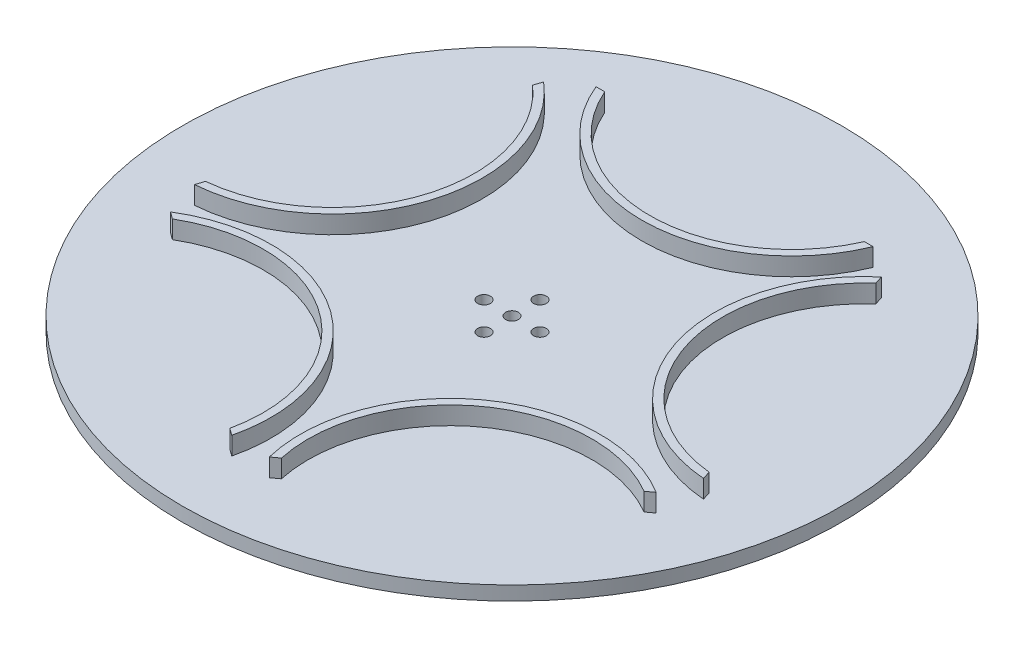
SolidWorks part; units mm, degrees
ref_plane "前视基准面" through (0, 0, 0) normal (0, 0, 1) x (1, 0, 0)
ref_plane "上视基准面" through (0, 0, 0) normal (0, 1, 0) x (1, 0, 0)
ref_plane "右视基准面" through (0, 0, 0) normal (1, 0, 0) x (0, 0, -1)
sketch "草图2" plane through (0, 0, 0) normal (0, 1, 0) x (1, 0, 0)
  line L0 (-32.5, 55.7171) -> (32.5, 55.7171) construction
  line L1 (-32.5, 55.7171) -> (-34.6735, 55.7171)
  line L2 (32.5, 55.7171) -> (34.6735, 55.7171)
  line L3 (42.9471, 48.1269) -> (42.2755, 50.194)
  line L4 (63.0332, -13.6918) -> (63.7048, -15.7589)
  line L5 (59.0428, -25.9731) -> (60.8011, -24.6956)
  line L6 (6.4567, -64.1791) -> (4.6983, -65.4567)
  line L7 (-6.4567, -64.1791) -> (-4.6983, -65.4567)
  line L8 (-59.0428, -25.9731) -> (-60.8011, -24.6956)
  line L9 (-63.0332, -13.6918) -> (-63.7048, -15.7589)
  line L10 (-42.9471, 48.1269) -> (-42.2755, 50.194)
  line L11 (0, 0) -> (0, 70) construction
  line L12 (0, 0) -> (66.574, 21.6312) construction
  circle A0 centre (0, 0) radius 82.5
  arc A1 (-34.6735, 55.7171) -> (34.6735, 55.7171) centre (0, 70) ccw
  arc A2 (-32.5, 55.7171) -> (32.5, 55.7171) centre (0, 70) ccw
  arc A3 (-37.3295, 73.5714) -> (-34.6735, 55.7171) centre (0, 70) ccw construction
  arc A4 (32.5, 55.7171) -> (-32.5, 55.7171) centre (0, 70) ccw construction
  arc A5 (34.6735, 55.7171) -> (-37.3295, 73.5714) centre (0, 70) ccw construction
  arc A6 (42.2755, 50.194) -> (63.7048, -15.7589) centre (66.574, 21.6312) ccw
  arc A7 (42.9471, 48.1269) -> (63.0332, -13.6918) centre (66.574, 21.6312) ccw
  arc A8 (60.8011, -24.6956) -> (4.6983, -65.4567) centre (41.145, -56.6312) ccw
  arc A9 (59.0428, -25.9731) -> (6.4567, -64.1791) centre (41.145, -56.6312) ccw
  arc A10 (-4.6983, -65.4567) -> (-60.8011, -24.6956) centre (-41.145, -56.6312) ccw
  arc A11 (-6.4567, -64.1791) -> (-59.0428, -25.9731) centre (-41.145, -56.6312) ccw
  arc A12 (-63.7048, -15.7589) -> (-42.2755, 50.194) centre (-66.574, 21.6312) ccw
  arc A13 (-63.0332, -13.6918) -> (-42.9471, 48.1269) centre (-66.574, 21.6312) ccw
  circle A14 centre (0, 0) radius 1.6
  circle A15 centre (0, 7) radius 1.6
  circle A19 centre (7, 0) radius 1.6
  circle A20 centre (0, -7) radius 1.6
  circle A21 centre (-7, 0) radius 1.6
  point P43 (0, 0)
  dimension "D1" = 75
  dimension "165" = 165
  dimension "D2" = 2
  dimension "D7" = 3.2
  dimension "D8" = 3.2
  dimension "D10" = 14
  dimension "D3" = 65
  dimension "D4" = 5
  dimension "D5" = 72
  dimension "D6" = 70
  dimension "D9" = 4
extrude "凸台-拉伸1" add sketch "草图2" along normal blind 3.5 contours A11 L7 A10 L8 | A0 A21 A20 A19 A15 A14 L1 A2 L2 A1 L3 A7 L4 A6 L5 A9 L6 A8 L7 A11 L8 A10 L9 A13 L10 A12 | A2 L1 A1 L2 | A9 L6 A8 L5 | A7 L4 A6 L3 | A12 L10 A13 L9 region at (0, 0, -33.7687) region at (-19.8461, 0, 27.3159) region at (-80.1665, 0, 0)
extrude "凸台-拉伸2" add sketch "草图2<3>" along normal blind 8 contours A9 L5 A8 L6 | A13 L10 A12 L9 | A11 L8 A10 L7 | A7 L4 A6 L3 | A2 L2 A1 L1 region at (19.8461, 0, 27.3159)
sketch "草图2<3>" plane through (0, 0, 0) normal (0, 1, 0) x (1, 0, 0) same geometry as "草图2"
